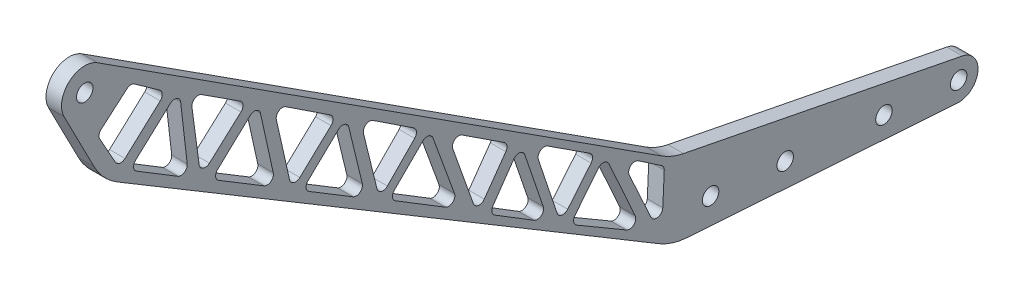
SolidWorks part; units mm, degrees
ref_plane "Front Plane" through (0, 0, 0) normal (0, 0, 1) x (1, 0, 0)
ref_plane "Top Plane" through (0, 0, 0) normal (0, 1, 0) x (1, 0, 0)
ref_plane "Right Plane" through (0, 0, 0) normal (1, 0, 0) x (0, 0, -1)
ref_plane "Plane1" through (-76.9133, 0, 0) normal (1, 0, 0) x (0, 0, -1)
sketch "Sketch1" plane through (-76.9133, 0, 0) normal (1, 0, 0) x (0, 0, -1)
  line L0 (535.7661, 896.8306) -> (535.7661, 915.8806) construction
  line L1 (434.1661, 906.5188) -> (434.1661, 925.5688) construction
  line L2 (177.8, 1090.4307) -> (434.1661, 925.5688) construction
  line L3 (139.7, 1090.4307) -> (177.8, 1090.4307) construction
  line L4 (535.7661, 896.8306) -> (535.7661, 915.8806) construction
  line L5 (434.1661, 906.5188) -> (434.1661, 925.5688) construction
  line L6 (177.8, 1090.4307) -> (434.1661, 925.5688) construction
  line L7 (139.7, 1090.4307) -> (177.8, 1090.4307) construction
  line L8 (535.2188, 907.962) -> (418.2911, 916.0438)
  line L9 (537.2996, 923.6685) -> (418.2911, 947.1021)
  line L10 (169.3326, 1086.0686) -> (184.9514, 1055.7506)
  line L11 (184.9514, 1055.7506) -> (418.2911, 916.0438)
  line L12 (418.2911, 947.1021) -> (182.9519, 1098.4422)
  line L13 (434.1661, 925.5688) -> (535.7661, 915.8806) construction
  circle A0 centre (177.8, 1090.4307) radius 3.3782
  circle A1 centre (434.1661, 925.5688) radius 3.3782
  circle A2 centre (535.7661, 915.8806) radius 3.3782
  arc A3 (535.2188, 907.962) -> (537.2996, 923.6685) centre (535.7661, 915.8806) ccw
  arc A5 (182.9519, 1098.4422) -> (169.3326, 1086.0686) centre (177.8, 1090.4307) ccw
  arc A6 (537.2996, 923.6685) -> (535.2188, 907.962) centre (535.7661, 915.8806) ccw construction
  arc A7 (169.3326, 1086.0686) -> (185.8114, 1085.2788) centre (177.8, 1090.4307) ccw construction
  arc A8 (185.8114, 1085.2788) -> (182.9519, 1098.4422) centre (177.8, 1090.4307) ccw construction
  circle A9 centre (464.7144, 922.6558) radius 3.3782
  circle A10 centre (505.1709, 918.798) radius 3.3782
  spline S0 degree 3 poles (935.6767, 939.7163) (940.3147, 942.1548) (935.2529, 940.0507) (930.9716, 938.764) (920.6916, 935.461) (907.9553, 931.9087) (891.2949, 927.4743) (871.5218, 922.6042) (848.5739, 917.4165) (822.7695, 912.1503) (794.3904, 907.0475) (763.8436, 902.4482) (731.6326, 898.5836) (698.2942, 895.5048) (664.3294, 893.3038) (630.2914, 892.1587) (596.9177, 892.4579) (565.0805, 894.155) (535.5455, 896.7257) (508.8897, 899.7641) (485.4664, 902.8148) (465.3261, 905.1664) (448.3721, 906.4646) (434.4368, 906.7165) (423.4463, 905.9074) (416.5733, 904.5379) (412.9407, 903.1204) (411.5732, 902.4729) (410.4746, 901.8174) (409.7947, 901.3358) (409.3397, 900.9203) (409.0422, 900.6195) (408.7846, 900.3039) (408.5873, 899.9553) (408.4178, 899.5844) (408.2374, 899.0451) (408.051, 898.3239) (407.9116, 897.2265) (407.8599, 894.9991) (408.6865, 890.8402) (411.376, 884.946) (416.2539, 878.2548) (423.1327, 871.4111) (431.9816, 864.5947) (442.7539, 857.9825) (455.382, 851.7275) (469.765, 845.9615) (485.7865, 840.8065) (503.3041, 836.37) (522.1586, 832.7575) (542.1676, 830.0521) (563.1459, 828.3505) (584.9266, 827.7965) (607.3492, 828.4639) (630.2782, 830.4035) (653.5854, 833.657) (677.1845, 838.2437) (700.9897, 844.1113) (724.9284, 850.9153) (748.8232, 858.3979) (772.4019, 866.3681) (795.3921, 874.6046) (817.5075, 882.9123) (838.4515, 891.1278) (857.9391, 899.0809) (875.6775, 906.6433) (891.4161, 913.7156) (904.9213, 920.2497) (916.21, 926.5709) (924.8872, 932.3286) (932.3848, 937.3638) (935.6767, 939.7163) (940.3147, 942.1548) (935.2529, 940.0507) knots -0.014576 -0.006911 -0.001813 0 0.001841 0.007308 0.016237 0.028456 0.043801 0.062126 0.08324 0.106896 0.132817 0.160613 0.189791 0.219873 0.250457 0.281127 0.311257 0.339999 0.366671 0.390812 0.411995 0.430069 0.445224 0.457619 0.467425 0.474786 0.47628 0.477884 0.47884 0.479711 0.480113 0.480492 0.480846 0.481203 0.481564 0.48194 0.482727 0.483559 0.484903 0.488692 0.494806 0.502149 0.510796 0.520764 0.532062 0.544666 0.558541 0.573612 0.589803 0.60701 0.625107 0.643967 0.663469 0.683551 0.704142 0.725196 0.74668 0.768633 0.790977 0.813463 0.835827 0.857772 0.879003 0.899228 0.918151 0.935487 0.950987 0.964428 0.975828 0.985424 0.993089 0.998187 1 1.001841 1.007308 1.016237 only from (939.324, 941.6889) to (939.324, 941.6889) construction
  spline S1 degree 3 poles (935.6767, 939.7163) (940.3147, 942.1548) (935.2529, 940.0507) (930.9716, 938.764) (920.6916, 935.461) (907.9553, 931.9087) (891.2949, 927.4743) (871.5218, 922.6042) (848.5739, 917.4165) (822.7695, 912.1503) (794.3904, 907.0475) (763.8436, 902.4482) (731.6326, 898.5836) (698.2942, 895.5048) (664.3294, 893.3038) (630.2914, 892.1587) (596.9177, 892.4579) (565.0805, 894.155) (535.5455, 896.7257) (508.8897, 899.7641) (485.4664, 902.8148) (465.3261, 905.1664) (448.3721, 906.4646) (434.4368, 906.7165) (423.4463, 905.9074) (416.5733, 904.5379) (412.9407, 903.1204) (411.5732, 902.4729) (410.4746, 901.8174) (409.7947, 901.3358) (409.3397, 900.9203) (409.0422, 900.6195) (408.7846, 900.3039) (408.5873, 899.9553) (408.4178, 899.5844) (408.2374, 899.0451) (408.051, 898.3239) (407.9116, 897.2265) (407.8599, 894.9991) (408.6865, 890.8402) (411.376, 884.946) (416.2539, 878.2548) (423.1327, 871.4111) (431.9816, 864.5947) (442.7539, 857.9825) (455.382, 851.7275) (469.765, 845.9615) (485.7865, 840.8065) (503.3041, 836.37) (522.1586, 832.7575) (542.1676, 830.0521) (563.1459, 828.3505) (584.9266, 827.7965) (607.3492, 828.4639) (630.2782, 830.4035) (653.5854, 833.657) (677.1845, 838.2437) (700.9897, 844.1113) (724.9284, 850.9153) (748.8232, 858.3979) (772.4019, 866.3681) (795.3921, 874.6046) (817.5075, 882.9123) (838.4515, 891.1278) (857.9391, 899.0809) (875.6775, 906.6433) (891.4161, 913.7156) (904.9213, 920.2497) (916.21, 926.5709) (924.8872, 932.3286) (932.3848, 937.3638) (935.6767, 939.7163) (940.3147, 942.1548) (935.2529, 940.0507) knots -0.014576 -0.006911 -0.001813 0 0.001841 0.007308 0.016237 0.028456 0.043801 0.062126 0.08324 0.106896 0.132817 0.160613 0.189791 0.219873 0.250457 0.281127 0.311257 0.339999 0.366671 0.390812 0.411995 0.430069 0.445224 0.457619 0.467425 0.474786 0.47628 0.477884 0.47884 0.479711 0.480113 0.480492 0.480846 0.481203 0.481564 0.48194 0.482727 0.483559 0.484903 0.488692 0.494806 0.502149 0.510796 0.520764 0.532062 0.544666 0.558541 0.573612 0.589803 0.60701 0.625107 0.643967 0.663469 0.683551 0.704142 0.725196 0.74668 0.768633 0.790977 0.813463 0.835827 0.857772 0.879003 0.899228 0.918151 0.935487 0.950987 0.964428 0.975828 0.985424 0.993089 0.998187 1 1.001841 1.007308 1.016237 only from (939.324, 941.6889) to (939.324, 941.6889) construction
  dimension "D1" = 6.7564
  dimension "D2" = 6.7564
  dimension "D3" = 6.7564
  dimension "D4" = 15.875
  dimension "D5" = 30
  dimension "D6" = 19.05
  dimension "D10" = 6.7564
  dimension "D11" = 6.7564
  dimension "D7" = 148.166
  dimension "D8" = 15.875
  dimension "D9" = 9.525
  dimension "D12" = 40.64
  dimension "D13" = 30.734
extrude "Boss-Extrude1" add sketch "Sketch1" along normal mid plane 6.35
fillet "Fillet1" radius 25.4 3 edges at (-76.9133, 1055.7506, -184.9514) (-76.9133, 947.1021, -418.2911) (-76.9133, 916.0438, -418.2911)
sketch "Sketch2" plane through (-73.7383, 0, 0) normal (1, 0, 0) x (0, 0, -1)
  line L6 (212.8295, 1069.041) -> (198.606, 1055.9934)
  line L7 (217.0697, 1067.4611) -> (219.7682, 1044.1331)
  line L8 (215.9263, 1041.6704) -> (199.0043, 1051.9508)
  line L9 (221.7077, 1063.3434) -> (224.6501, 1041.3976)
  line L10 (228.8738, 1039.8536) -> (241.7874, 1051.5641)
  line L11 (241.4587, 1055.5797) -> (225.6027, 1065.815)
  line L12 (249.7605, 1047.1075) -> (255.0131, 1023.357)
  line L13 (251.218, 1020.6354) -> (232.6267, 1031.8852)
  line L14 (232.2048, 1035.9116) -> (245.5435, 1048.4123)
  line L15 (256.2887, 1041.5496) -> (261.6992, 1017.5322)
  line L16 (265.9184, 1016.2413) -> (278.6819, 1028.2603)
  line L17 (278.34, 1032.2292) -> (260.166, 1044.2275)
  line L18 (285.9508, 1024.1277) -> (291.4891, 1001.274)
  line L19 (287.7049, 998.503) -> (269.6883, 1009.4129)
  line L20 (269.2476, 1013.4205) -> (281.7259, 1025.3644)
  line L21 (291.9877, 1018.7934) -> (297.5035, 996.4443)
  line L22 (301.7822, 995.2737) -> (312.9339, 1006.6348)
  line L23 (312.5193, 1010.5347) -> (295.8517, 1021.5227)
  line L24 (320.4317, 1003.0426) -> (329.2353, 978.9361)
  line L25 (325.5244, 975.8978) -> (305.073, 988.4025)
  line L26 (304.6055, 992.3691) -> (316.2534, 1003.9709)
  line L27 (328.5613, 995.1219) -> (337.0009, 971.414)
  line L28 (341.465, 970.7956) -> (350.2883, 983.2249)
  line L29 (349.6064, 986.8216) -> (332.3434, 998.1001)
  line L30 (358.0244, 978.3225) -> (365.6133, 956.0674)
  line L31 (361.8794, 953.0835) -> (345.7383, 963.0022)
  line L32 (344.9806, 966.6134) -> (353.5329, 978.9499)
  line L33 (363.6159, 973.7211) -> (371.269, 950.9287)
  line L34 (375.6344, 950.1187) -> (385.2284, 961.7217)
  line L35 (384.6533, 965.4711) -> (367.4062, 976.6604)
  line L36 (388.1861, 958.4199) -> (378.5999, 946.4446)
  line L37 (379.3, 942.665) -> (399.6766, 930.7417)
  line L38 (403.2744, 933.9792) -> (392.484, 957.8779)
  line L39 (400.8201, 949.6856) -> (409.729, 930.2453)
  line L40 (414.5753, 931.1847) -> (415.1835, 944.1767)
  line L41 (414.071, 946.3983) -> (404.5539, 952.8466)
  line L42 (208.7115, 1072.0152) -> (194.2879, 1058.8022)
  line L43 (190.3558, 1059.4345) -> (183.9642, 1070.8533)
  line L44 (184.5202, 1074.0161) -> (195.0647, 1083.1245)
  line L45 (198.1985, 1083.2713) -> (208.4691, 1075.9571)
  arc A0 (194.2879, 1058.8022) -> (190.3558, 1059.4345) centre (192.5722, 1060.6752) cw
  arc A1 (208.7115, 1072.0152) -> (208.4691, 1075.9571) centre (206.9957, 1073.8881) ccw
  arc A2 (415.1835, 944.1767) -> (414.071, 946.3983) centre (412.6462, 944.2955) ccw
  arc A3 (400.8201, 949.6856) -> (404.5539, 952.8466) centre (403.1292, 950.7438) cw
  arc A4 (409.729, 930.2453) -> (414.5753, 931.1847) centre (412.038, 931.3034) ccw
  arc A5 (399.6766, 930.7417) -> (403.2744, 933.9792) centre (400.9594, 932.934) ccw
  arc A6 (378.5999, 946.4446) -> (379.3, 942.665) centre (380.5828, 944.8573) ccw
  arc A7 (388.1861, 958.4199) -> (392.484, 957.8779) centre (390.169, 956.8326) cw
  arc A8 (385.2284, 961.7217) -> (384.6533, 965.4711) centre (383.2709, 963.3403) ccw
  arc A9 (363.6159, 973.7211) -> (367.4062, 976.6604) centre (366.0238, 974.5296) cw
  arc A10 (371.269, 950.9287) -> (375.6344, 950.1187) centre (373.6769, 951.7373) ccw
  arc A11 (365.6133, 956.0674) -> (361.8794, 953.0835) centre (363.2092, 955.2476) cw
  arc A12 (345.7383, 963.0022) -> (344.9806, 966.6134) centre (347.0681, 965.1663) cw
  arc A13 (358.0244, 978.3225) -> (353.5329, 978.9499) centre (355.6204, 977.5028) ccw
  arc A14 (328.5613, 995.1219) -> (332.3434, 998.1001) centre (330.9542, 995.9737) cw
  arc A15 (350.2883, 983.2249) -> (349.6064, 986.8216) centre (348.2171, 984.6952) ccw
  arc A16 (341.465, 970.7956) -> (337.0009, 971.414) centre (339.3938, 972.2659) cw
  arc A17 (329.2353, 978.9361) -> (325.5244, 975.8978) centre (326.8494, 978.0648) cw
  arc A18 (320.4317, 1003.0426) -> (316.2534, 1003.9709) centre (318.0459, 1002.1713) ccw
  arc A19 (305.073, 988.4025) -> (304.6055, 992.3691) centre (306.398, 990.5695) cw
  arc A20 (297.5035, 996.4443) -> (301.7822, 995.2737) centre (299.9695, 997.0529) ccw
  arc A21 (312.9339, 1006.6348) -> (312.5193, 1010.5347) centre (311.1213, 1008.4141) ccw
  arc A22 (291.9877, 1018.7934) -> (295.8517, 1021.5227) centre (294.4537, 1019.4021) cw
  arc A23 (291.4891, 1001.274) -> (287.7049, 998.503) centre (289.0205, 1000.6757) cw
  arc A24 (269.6883, 1009.4129) -> (269.2476, 1013.4205) centre (271.0039, 1011.5856) cw
  arc A25 (285.9508, 1024.1277) -> (281.7259, 1025.3644) centre (283.4822, 1023.5295) ccw
  arc A26 (256.2887, 1041.5496) -> (260.166, 1044.2275) centre (258.7666, 1042.1078) cw
  arc A27 (278.6819, 1028.2603) -> (278.34, 1032.2292) centre (276.9406, 1030.1094) ccw
  arc A28 (265.9184, 1016.2413) -> (261.6992, 1017.5322) centre (264.1771, 1018.0904) cw
  arc A29 (255.0131, 1023.357) -> (251.218, 1020.6354) centre (252.533, 1022.8085) cw
  arc A30 (232.6267, 1031.8852) -> (232.2048, 1035.9116) centre (233.9417, 1034.0583) cw
  arc A31 (249.7605, 1047.1075) -> (245.5435, 1048.4123) centre (247.2804, 1046.559) ccw
  arc A32 (221.7077, 1063.3434) -> (225.6027, 1065.815) centre (224.2251, 1063.6809) cw
  arc A33 (241.7874, 1051.5641) -> (241.4587, 1055.5797) centre (240.0812, 1053.4457) ccw
  arc A34 (224.6501, 1041.3976) -> (228.8738, 1039.8536) centre (227.1675, 1041.7351) ccw
  arc A35 (219.7682, 1044.1331) -> (215.9263, 1041.6704) centre (217.2451, 1043.8412) cw
  arc A36 (212.8295, 1069.041) -> (217.0697, 1067.4611) centre (214.5465, 1067.1693) cw
  arc A37 (198.606, 1055.9934) -> (199.0043, 1051.9508) centre (200.3231, 1054.1216) ccw
  arc A38 (183.9642, 1070.8533) -> (184.5202, 1074.0161) centre (186.1806, 1072.0939) cw
  arc A39 (195.0647, 1083.1245) -> (198.1985, 1083.2713) centre (196.7251, 1081.2023) cw
  dimension "D1" = 2.54
  dimension "D2" = 2.54
extrude "Cut-Extrude3" cut sketch "Sketch2" against normal through all
